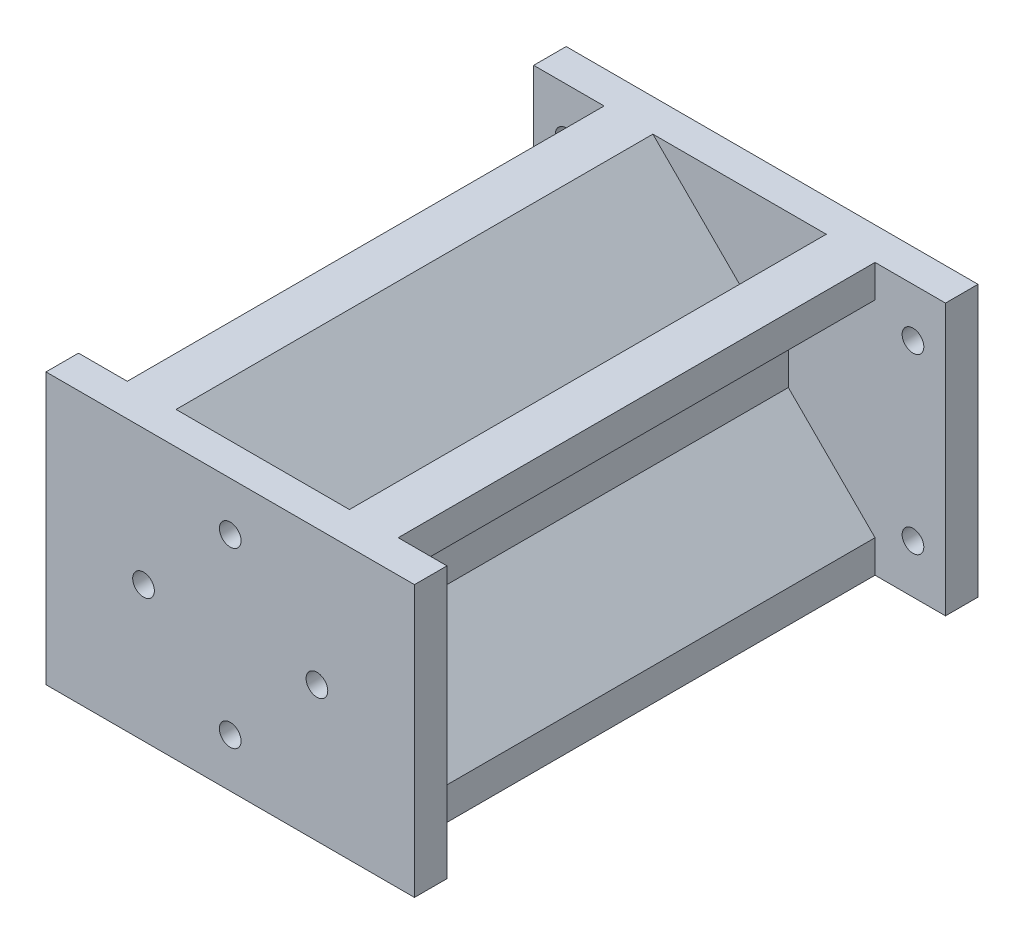
SolidWorks part; units mm, degrees
ref_plane "前视基准面" through (0, 0, 0) normal (0, 0, 1) x (1, 0, 0)
ref_plane "上视基准面" through (0, 0, 0) normal (0, 1, 0) x (1, 0, 0)
ref_plane "右视基准面" through (0, 0, 0) normal (1, 0, 0) x (0, 0, -1)
sketch "草图1" plane through (0, 0, 0) normal (0, 0, 1) x (1, 0, 0)
  line L0 (-45.6567, 0) -> (41.5448, 0) construction
  line L1 (-12.5, 12.5) -> (12.5, 12.5)
  line L2 (-12.5, 12.5) -> (-12.5, -12.5)
  line L3 (-12.5, -12.5) -> (12.5, -12.5)
  line L4 (12.5, 12.5) -> (12.5, -12.5)
  line L5 (0, 58.7621) -> (0, -33.7621) construction
  point P9 (0, 12.5)
  point P10 (12.5, 0)
  dimension "D1" = 25
  dimension "D2" = 25
extrude "凸台-拉伸1" add sketch "草图1" along normal blind 44
sketch "草图2" plane through (0, 0, 0) normal (0, 0, -1) x (-1, 0, 0)
  line L0 (-12.5, -12.5) -> (-12.5, 12.5) construction
  line L1 (-12.5, 9.5) -> (-4.5, 9.5)
  line L2 (-12.5, 9.5) -> (-12.5, -9.5)
  line L3 (-12.5, -9.5) -> (-4.5, -9.5)
  line L4 (-4.5, 9.5) -> (-4.5, -9.5)
  line L5 (-12.5, 12.5) -> (12.5, 12.5) construction
  line L6 (12.5, -12.5) -> (-12.5, -12.5) construction
  line L7 (-12.5, 9.5) -> (-4.5, 1.5)
  line L8 (-12.5, -9.5) -> (-4.5, -1.5)
  line M3 (-12.5, 12.5) -> (-12.5, -12.5)
  dimension "D1" = 8
  dimension "D2" = 3
  dimension "D3" = 3
  dimension "D4" = 45
  dimension "D5" = 45
extrude "切除-拉伸1" cut sketch "草图2" against normal blind 100 contours L8 L4 L7 M3 region at (9.4697, 0, 0)
mirror "镜向1" about plane through (0, 0, 0) normal (1, 0, 0) of "切除-拉伸1"
sketch "草图9" plane through (0, 0, 0) normal (0, 0, -1) x (-1, 0, 0)
  line L0 (0, 23.4554) -> (0, -17.569) construction
  line L1 (-8, 12.5) -> (0, 4.5)
  line L2 (-12.5, 12.5) -> (12.5, 12.5) construction
  line L3 (0, 4.5) -> (8, 12.5)
  line L4 (8, 12.5) -> (-8, 12.5)
  dimension "D1" = 45
  dimension "D2" = 45
  dimension "D3" = 16
extrude "切除-拉伸4" cut sketch "草图9" against normal up to surface (44 mm away) contours L1 L3 L4 up to face at (0, 0, 44)
mirror "镜向2" about plane through (0, 0, 0) normal (0, 1, 0) of "切除-拉伸4"
sketch "草图3" plane through (0, 0, 0) normal (0, 0, -1) x (-1, 0, 0)
  line L1 (-19, 12.5) -> (19, 12.5)
  line L2 (-19, 12.5) -> (-19, -12.5)
  line L3 (-19, -12.5) -> (19, -12.5)
  line L4 (19, 12.5) -> (19, -12.5)
  line L5 (0, 22.1705) -> (0, -27.6173) construction
  line L15 (12.5, -9.5) -> (4.5, -1.5)
  line L16 (4.5, 1.5) -> (12.5, 9.5)
  line L17 (12.5, 9.5) -> (12.5, 12.5)
  line L18 (12.5, 12.5) -> (8, 12.5)
  line L19 (-12.5, 12.5) -> (-12.5, 9.5)
  line L20 (-12.5, 9.5) -> (-4.5, 1.5)
  line L21 (-4.5, -1.5) -> (-12.5, -9.5)
  line L22 (-12.5, -9.5) -> (-12.5, -12.5)
  line L23 (-12.5, -12.5) -> (-8, -12.5)
  line L24 (12.5, -12.5) -> (12.5, -9.5)
  line L25 (12.5, -9.5) -> (4.5, -1.5)
  line L26 (4.5, 1.5) -> (12.5, 9.5)
  line L27 (12.5, 9.5) -> (12.5, 12.5)
  line L28 (12.5, 12.5) -> (8, 12.5)
  line L29 (-12.5, 12.5) -> (-12.5, 9.5)
  line L30 (-12.5, 9.5) -> (-4.5, 1.5)
  line L31 (-4.5, -1.5) -> (-12.5, -9.5)
  line L32 (-12.5, -9.5) -> (-12.5, -12.5)
  line L33 (-12.5, -12.5) -> (-8, -12.5)
  line L34 (12.5, -12.5) -> (12.5, -9.5)
  line L38 (4.5, -1.5) -> (4.5, 1.5)
  line L39 (4.5, -1.5) -> (4.5, 1.5)
  line L40 (-4.5, 1.5) -> (-4.5, -1.5)
  line L41 (-4.5, 1.5) -> (-4.5, -1.5)
  line L47 (-8, -12.5) -> (0, -4.5)
  line L48 (-8, -12.5) -> (0, -4.5)
  line L49 (0, -4.5) -> (8, -12.5)
  line L50 (0, -4.5) -> (8, -12.5)
  line L51 (8, -12.5) -> (12.5, -12.5)
  line L52 (8, -12.5) -> (12.5, -12.5)
  line L53 (8, 12.5) -> (0, 4.5)
  line L54 (8, 12.5) -> (0, 4.5)
  line L55 (0, 4.5) -> (-8, 12.5)
  line L56 (0, 4.5) -> (-8, 12.5)
  line L57 (-8, 12.5) -> (-12.5, 12.5)
  line L58 (-8, 12.5) -> (-12.5, 12.5)
  point P19 (0, 12.5)
  dimension "D2" = 38
  dimension "D1" = 0
extrude "凸台-拉伸2" add sketch "草图3" along normal blind 3 contours L1 L4 L3 L2
sketch "草图4" plane through (0, 0, -3) normal (0, 0, -1) x (-1, 0, 0)
  line L0 (0, 20.8506) -> (0, -22.3365) construction
  line L1 (-22.6868, 0) -> (23.8554, 0) construction
  circle A0 centre (-16, 8) radius 1
  dimension "D1" = 2
  dimension "D3" = 8
  dimension "D2" = 16
extrude "切除-拉伸2" cut sketch "草图4" against normal blind 3
pattern_linear "阵列(线性)1" count 2 spacing 32 along (-1, 0, 0) of "切除-拉伸2"
pattern_linear "阵列(线性)2" count 2 spacing 16 along (0, -1, 0) of "阵列(线性)1"
sketch "草图6" plane through (0, 0, -3) normal (0, 0, -1) x (-1, 0, 0)
  line L0 (0, 16.0793) -> (0, -21.177) construction
  line L1 (-4.95, 2.9) -> (4.95, 2.9)
  line L2 (-4.95, 2.9) -> (-4.95, -2.9)
  line L3 (-4.95, -2.9) -> (4.95, -2.9)
  line L4 (4.95, 2.9) -> (4.95, -2.9)
  line L5 (-23.7636, 0) -> (23.1777, 0) construction
  point P9 (0, -2.9)
  point P10 (4.95, 0)
  dimension "D1" = 9.9
  dimension "D2" = 5.8
extrude "凸台-拉伸3" add sketch "草图6" along normal blind 3
sketch "草图7" plane through (0, 0, 44) normal (0, 0, 1) x (1, 0, 0)
  line L0 (0, 16.9996) -> (0, -15.9877) construction
  line L1 (-17, 12.5) -> (17, 12.5)
  line L2 (-17, 12.5) -> (-17, -12.5)
  line L3 (-17, -12.5) -> (17, -12.5)
  line L4 (17, 12.5) -> (17, -12.5)
  line L12 (-4.5, 1.5) -> (-4.5, -1.5)
  line L13 (-4.5, -1.5) -> (-12.5, -9.5)
  line L14 (-12.5, -9.5) -> (-12.5, -12.5)
  line L15 (-12.5, -12.5) -> (-8, -12.5)
  line L16 (12.5, -12.5) -> (12.5, -9.5)
  line L17 (12.5, -9.5) -> (4.5, -1.5)
  line L18 (4.5, -1.5) -> (4.5, 1.5)
  line L19 (4.5, 1.5) -> (12.5, 9.5)
  line L20 (12.5, 9.5) -> (12.5, 12.5)
  line L21 (12.5, 12.5) -> (8, 12.5)
  line L22 (-12.5, 12.5) -> (-12.5, 9.5)
  line L23 (-12.5, 9.5) -> (-4.5, 1.5)
  line L24 (-4.5, 1.5) -> (-4.5, -1.5)
  line L25 (-4.5, -1.5) -> (-12.5, -9.5)
  line L26 (-12.5, -9.5) -> (-12.5, -12.5)
  line L27 (-12.5, -12.5) -> (-8, -12.5)
  line L28 (12.5, -12.5) -> (12.5, -9.5)
  line L29 (12.5, -9.5) -> (4.5, -1.5)
  line L30 (4.5, -1.5) -> (4.5, 1.5)
  line L31 (4.5, 1.5) -> (12.5, 9.5)
  line L32 (12.5, 9.5) -> (12.5, 12.5)
  line L33 (12.5, 12.5) -> (8, 12.5)
  line L34 (-12.5, 12.5) -> (-12.5, 9.5)
  line L35 (-12.5, 9.5) -> (-4.5, 1.5)
  line L46 (-8, -12.5) -> (0, -4.5)
  line L47 (-8, -12.5) -> (0, -4.5)
  line L48 (0, -4.5) -> (8, -12.5)
  line L49 (0, -4.5) -> (8, -12.5)
  line L50 (8, -12.5) -> (12.5, -12.5)
  line L51 (8, -12.5) -> (12.5, -12.5)
  line L52 (8, 12.5) -> (0, 4.5)
  line L53 (8, 12.5) -> (0, 4.5)
  line L54 (0, 4.5) -> (-8, 12.5)
  line L55 (0, 4.5) -> (-8, 12.5)
  line L56 (-8, 12.5) -> (-12.5, 12.5)
  line L57 (-8, 12.5) -> (-12.5, 12.5)
  point P17 (0, 12.5)
  dimension "D2" = 34
  dimension "D1" = 0
extrude "凸台-拉伸4" add sketch "草图7" along normal blind 3 contours L3 L4 L1 L2
sketch "草图8" plane through (0, 0, 47) normal (0, 0, 1) x (1, 0, 0)
  line L0 (0, 19.1963) -> (0, -19.5717) construction
  line L1 (-26.3315, 0) -> (26.9109, 0) construction
  circle A0 centre (0, 8) radius 1
  dimension "D1" = 2
  dimension "D2" = 8
extrude "切除-拉伸3" cut sketch "草图8" against normal blind 3
ref_axis "基准轴1" through (0, 0, -9.95) along (0, 0, 1)
pattern_circular "阵列(圆周)1" count 4 over 360 about axis through (0, 0, -9.95) along (0, 0, 1) of "切除-拉伸3"
